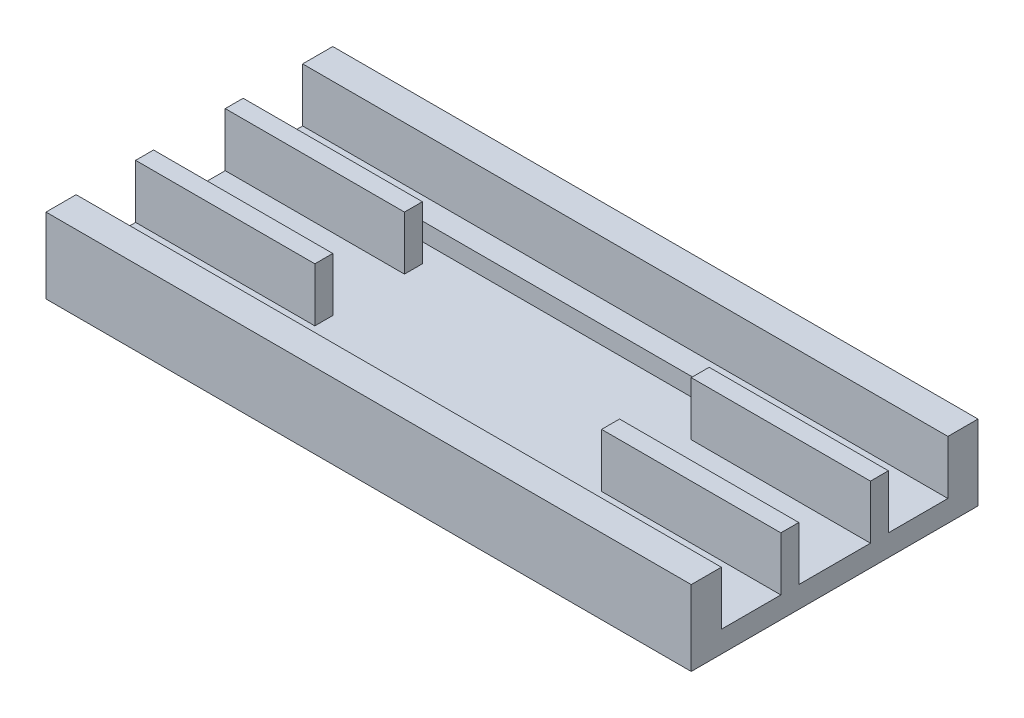
SolidWorks part; units mm, degrees
ref_plane "Front Plane" through (0, 0, 0) normal (0, 0, 1) x (1, 0, 0)
ref_plane "Top Plane" through (0, 0, 0) normal (0, 1, 0) x (1, 0, 0)
ref_plane "Right Plane" through (0, 0, 0) normal (1, 0, 0) x (0, 0, -1)
sketch "Sketch2" plane through (0, 0, 0) normal (0, 1, 0) x (1, 0, 0)
  line L1 (0, 0) -> (228.6, 0)
  line L2 (0, 0) -> (0, 101.6)
  line L3 (0, 101.6) -> (228.6, 101.6)
  line L4 (228.6, 0) -> (228.6, 101.6)
  dimension "D1" = 228.6
  dimension "D2" = 101.6
extrude "Boss-Extrude1" add sketch "Sketch2" along normal blind 7.62
sketch "Sketch3" plane through (0, 7.62, 0) normal (0, 1, 0) x (1, 0, 0)
  line L0 (228.6, 0) -> (228.6, 101.6) construction
  line L5 (0, 101.6) -> (0, 0) construction
  line L6 (228.6, 0) -> (0, 0)
  line L7 (228.6, 0) -> (228.6, 10.668)
  line L8 (228.6, 10.668) -> (0, 10.668)
  line L9 (0, 0) -> (0, 10.668)
  line L10 (0, 50.8) -> (228.6, 50.8) construction
  line L15 (0, 31.75) -> (63.5, 31.75)
  line L16 (0, 31.75) -> (0, 38.1)
  line L17 (0, 38.1) -> (63.5, 38.1)
  line L18 (228.6, 31.75) -> (228.6, 38.1)
  line L19 (228.6, 69.85) -> (228.6, 63.5)
  line L20 (0, 69.85) -> (0, 63.5)
  line L21 (0, 69.85) -> (63.5, 69.85)
  line L22 (0, 63.5) -> (63.5, 63.5)
  line L23 (228.6, 90.932) -> (0, 90.932)
  line L24 (0, 101.6) -> (0, 90.932)
  line L25 (228.6, 101.6) -> (0, 101.6)
  line L26 (228.6, 101.6) -> (228.6, 90.932)
  line L27 (63.5, 38.1) -> (63.5, 31.75)
  line L28 (165.1, 38.1) -> (165.1, 31.75)
  line L29 (165.1, 31.75) -> (228.6, 31.75)
  line L30 (165.1, 38.1) -> (228.6, 38.1)
  line L31 (63.5, 63.5) -> (63.5, 69.85)
  line L32 (165.1, 63.5) -> (165.1, 69.85)
  line L33 (165.1, 69.85) -> (228.6, 69.85)
  line L34 (165.1, 63.5) -> (228.6, 63.5)
  point P22 (0, 50.8)
  dimension "D1" = 10.668
  dimension "D2" = 63.5
  dimension "D5" = 6.35
  dimension "D6" = 12.7
extrude "Boss-Extrude2" add sketch "Sketch3" along normal blind 19.05
sketch "Sketch4" plane through (0, 7.62, 0) normal (0, 1, 0) x (1, 0, 0)
  line L0 (25.4, 21.7986) -> (203.2, 21.7986) construction
  line L1 (25.4, 24.9736) -> (203.2, 24.9736)
  line L2 (25.4, 18.6236) -> (203.2, 18.6236)
  line L5 (0, 50.8) -> (228.6, 50.8) construction
  line L6 (0, 63.5) -> (0, 38.1) construction
  line L7 (228.6, 38.1) -> (228.6, 63.5) construction
  line L8 (25.4, 79.8014) -> (203.2, 79.8014) construction
  line L9 (25.4, 76.6264) -> (203.2, 76.6264)
  line L10 (25.4, 82.9764) -> (203.2, 82.9764)
  line L16 (228.6, 10.668) -> (0, 10.668) construction
  arc A0 (25.4, 24.9736) -> (25.4, 18.6236) centre (25.4, 21.7986) ccw
  arc A1 (203.2, 18.6236) -> (203.2, 24.9736) centre (203.2, 21.7986) ccw
  arc A2 (25.4, 76.6264) -> (25.4, 82.9764) centre (25.4, 79.8014) cw
  arc A3 (203.2, 82.9764) -> (203.2, 76.6264) centre (203.2, 79.8014) cw
  point P2 (114.3, 21.7986)
  point P17 (114.3, 79.8014)
  dimension "D1" = 11.1306
  dimension "D2" = 177.8
  dimension "D3" = 114.3
  dimension "D4" = 6.35
extrude "Cut-Extrude1" cut sketch "Sketch4" against normal through all
